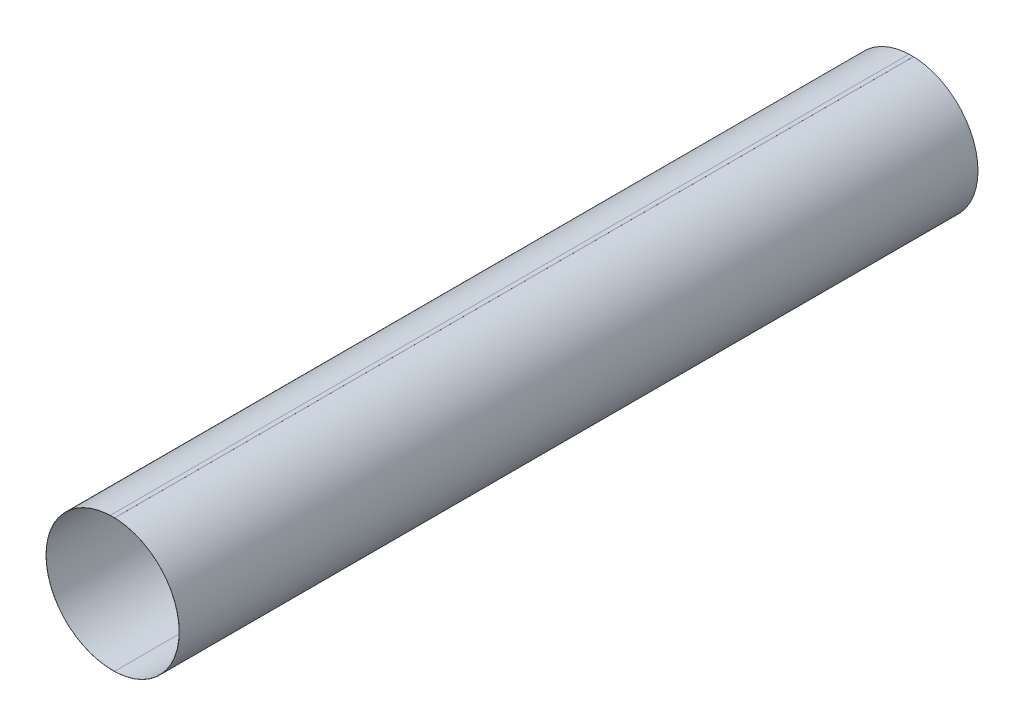
SolidWorks part; units mm, degrees
material "PVC Rigid"
ref_plane "Front Plane" through (0, 0, 0) normal (1, 0, 0) x (0, 1, 0)
ref_plane "Top Plane" through (0, 0, 0) normal (0, 0, 1) x (0, 1, 0)
ref_plane "Right Plane" through (0, 0, 0) normal (0, 1, 0) x (-1, 0, 0)
sketch "Sketch4" plane through (0, 0, 0) normal (0, 0, 1) x (0, 1, 0)
  arc A1 (-152.318, -5) -> (152.318, -5) centre (0, 0) cw
  arc A2 (-152.318, 5) -> (152.318, 5) centre (0, 0) ccw
  point P7 (0, 0)
  point P8 (0, 0)
  point P9 (0, 0)
  dimension "D1" = 152.4
  dimension "D2" = 10
extrude "Extrude-Thin4" add sketch "Sketch4" along normal blind 1828.8 thin contours A1 thin type one direction wall 0.254
extrude "Extrude-Thin5" add sketch "Sketch4<4>" along normal blind 1828.8 separate body thin contours A2 thin type one direction wall 0.254
sketch "Sketch4<4>" plane through (0, 0, 0) normal (0, 0, 1) x (0, 1, 0) same geometry as "Sketch4"
